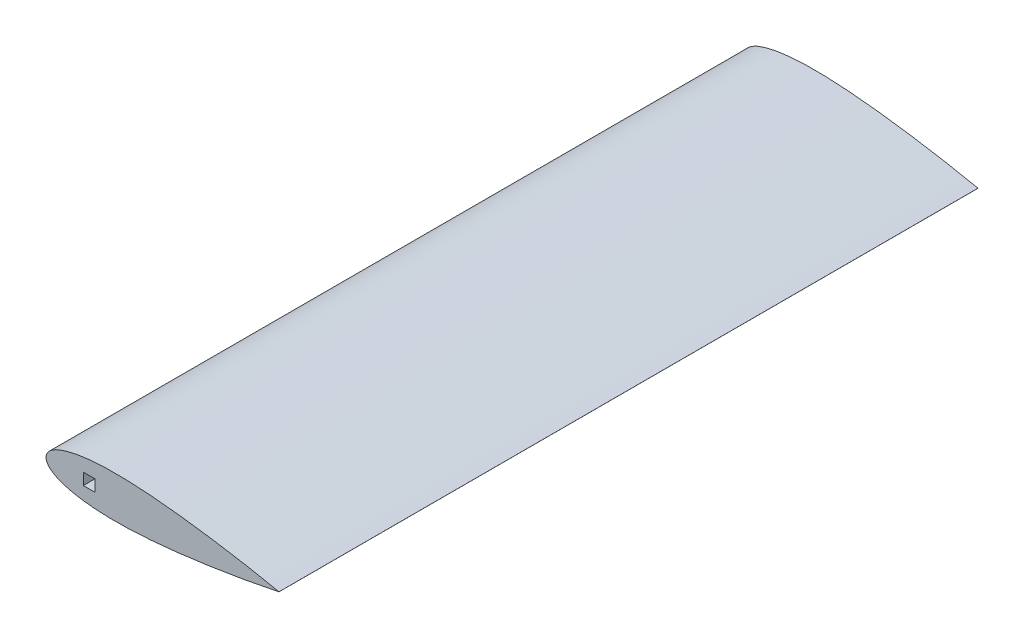
SolidWorks part; units mm, degrees
material "polystirene foam"
ref_plane "Front Plane" through (0, 0, 0) normal (0, 0, 1) x (1, 0, 0)
ref_plane "Top Plane" through (0, 0, 0) normal (0, 1, 0) x (1, 0, 0)
ref_plane "Right Plane" through (0, 0, 0) normal (1, 0, 0) x (0, 0, -1)
curve "Curve1"
  spline degree 3 poles (267.933, 0.5337, 0) (270.49, -0.1564, 0) (268.2375, 0.6665, 0) (266.5672, 1.4668, 0) (262.6756, 3.0154, 0) (257.9132, 4.5724, 0) (251.732, 6.3325, 0) (244.4112, 8.2376, 0) (235.9576, 10.2728, 0) (226.5142, 12.3893, 0) (216.1934, 14.5409, 0) (205.1313, 16.6775, 0) (193.4567, 18.7298, 0) (181.2977, 20.6324, 0) (168.7678, 22.3117, 0) (155.9753, 23.7079, 0) (143.0353, 24.8049, 0) (130.0617, 25.5802, 0) (117.1734, 26.0003, 0) (104.4837, 26.0576, 0) (92.1044, 25.7531, 0) (80.1395, 25.0742, 0) (68.69, 24.0381, 0) (57.8509, 22.6699, 0) (47.7143, 21.0125, 0) (38.3732, 19.0872, 0) (29.9084, 16.9558, 0) (22.399, 14.6444, 0) (15.9079, 12.2159, 0) (10.4843, 9.7202, 0) (6.177, 7.2209, 0) (2.9612, 4.7412, 0) (0.9766, 2.4261, 0) (0.0237, 0.7907, 0) (-0.0162, -0.4697, 0) (0.8003, -1.8361, 0) (3.4921, -2.6295, 0) (7.308, -3.6627, 0) (12.6566, -4.3991, 0) (19.3194, -5.0329, 0) (27.2905, -5.4698, 0) (36.4622, -5.7387, 0) (46.7414, -5.84, 0) (58.0105, -5.7702, 0) (70.1434, -5.5368, 0) (83.0071, -5.1408, 0) (96.4629, -4.5659, 0) (110.374, -3.827, 0) (124.6167, -2.893, 0) (139.0995, -1.7363, 0) (153.7348, -0.4008, 0) (168.4097, 0.8923, 0) (182.9339, 2.0414, 0) (197.0782, 2.9592, 0) (210.6044, 3.579, 0) (223.2667, 3.8744, 0) (234.8405, 3.8186, 0) (245.0477, 3.4533, 0) (253.7786, 2.7629, 0) (260.4407, 1.9422, 0) (265.7815, 0.9299, 0) (267.933, 0.5337, 0) (270.49, -0.1564, 0) (268.2375, 0.6665, 0) knots -0.016249 -0.007187 -0.001789 0 0.001694 0.006395 0.013462 0.022754 0.034367 0.048191 0.064031 0.081681 0.100894 0.121432 0.143025 0.165434 0.188439 0.211855 0.235496 0.259144 0.282615 0.305702 0.328232 0.35003 0.370944 0.390817 0.409506 0.426857 0.442733 0.457018 0.469615 0.48045 0.489472 0.49673 0.502329 0.506256 0.506442 0.509182 0.513914 0.521178 0.530944 0.543145 0.55767 0.574384 0.59311 0.613638 0.635744 0.659184 0.683714 0.709076 0.735036 0.76143 0.788184 0.815057 0.841645 0.867514 0.892232 0.915364 0.936485 0.9552 0.971104 0.983751 0.992813 0.998211 1 1.001694 1.006395 1.013462 periodic
curve "Curve2"
  spline degree 3 poles (1, 0.0019, 0) (0.9833, 0.0053, 0) (0.9501, 0.0122, 0) (0.8834, 0.025, 0) (0.8002, 0.0397, 0) (0.7001, 0.0553, 0) (0.6002, 0.0688, 0) (0.5002, 0.0799, 0) (0.4001, 0.0878, 0) (0.3167, 0.0906, 0) (0.25, 0.0895, 0) (0.1999, 0.0865, 0) (0.1497, 0.0808, 0) (0.1079, 0.0728, 0) (0.0746, 0.0633, 0) (0.0492, 0.0537, 0) (0.0279, 0.0421, 0) (0.0083, 0.0261, 0) (-0.0054, 0, 0) (0.0083, -0.0261, 0) (0.0279, -0.0421, 0) (0.0492, -0.0537, 0) (0.0746, -0.0633, 0) (0.1079, -0.0728, 0) (0.1497, -0.0808, 0) (0.1999, -0.0865, 0) (0.25, -0.0895, 0) (0.3167, -0.0906, 0) (0.4001, -0.0878, 0) (0.5002, -0.0799, 0) (0.6002, -0.0688, 0) (0.7001, -0.0553, 0) (0.8002, -0.0397, 0) (0.8834, -0.025, 0) (0.9501, -0.0122, 0) (0.9833, -0.0053, 0) (1, -0.0019, 0) knots 0 0 0 0 0.024604 0.049152 0.098109 0.146905 0.195555 0.244056 0.29241 0.340644 0.364754 0.388906 0.413178 0.437756 0.450305 0.46323 0.477068 0.485036 0.5 0.514964 0.522932 0.53677 0.549695 0.562244 0.586822 0.611094 0.635246 0.659356 0.70759 0.755944 0.804445 0.853095 0.901891 0.950848 0.975396 1 1 1 1
sketch "Sketch2" plane through (0, 0, 0) normal (0, 0, 1) x (1, 0, 0)
  line L1 (0, 0) -> (200, 0) construction
  line L2 (0, 5.3617) -> (0, 0) construction
  line L3 (200, 0.026) -> (200, -0.026)
  line L4 (0, 17.8541) -> (200, 17.8541) construction
  line L5 (0, -17.8541) -> (200, -17.8541) construction
  spline S1 degree 3 poles (200, 0.026) (196.1337, 0.8245) (188.9731, 2.314) (175.1972, 4.9535) (158.6821, 7.8644) (138.8483, 10.963) (119.0176, 13.6524) (99.1866, 15.8519) (79.3508, 17.4108) (62.8016, 17.9646) (49.5701, 17.7436) (39.6384, 17.1555) (29.688, 16.02) (21.4064, 14.4333) (14.8011, 12.5462) (9.7569, 10.6396) (5.5318, 8.3438) (1.6454, 5.1683) (-1.0737, 0) (1.6454, -5.1683) (5.5318, -8.3438) (9.7569, -10.6396) (14.8011, -12.5462) (21.4064, -14.4333) (29.688, -16.02) (39.6384, -17.1555) (49.5701, -17.7436) (62.8016, -17.9646) (79.3508, -17.4108) (99.1866, -15.8519) (119.0176, -13.6524) (138.8483, -10.963) (158.6821, -7.8644) (175.1972, -4.9535) (188.9731, -2.314) (196.1337, -0.8245) (200, -0.026) knots -0.00419 -0.00419 -0.00419 -0.00419 0.024604 0.049152 0.098109 0.146905 0.195555 0.244056 0.29241 0.340644 0.364754 0.388906 0.413178 0.437756 0.450305 0.46323 0.477068 0.485036 0.5 0.514964 0.522932 0.53677 0.549695 0.562244 0.586822 0.611094 0.635246 0.659356 0.70759 0.755944 0.804445 0.853095 0.901891 0.950848 0.975396 1.00419 1.00419 1.00419 1.00419
  dimension "D1" = 200
extrude "Boss-Extrude1" add sketch "Sketch2" along normal blind 600 contours S1 L3
sketch "Sketch3" plane through (0, 0, 600) normal (0, 0, 1) x (1, 0, 0)
  line L0 (0, 0) -> (20, 0)
  line L1 (0, 0) -> (200, 0) construction
  line L2 (20, 0) -> (30, 0)
  line L3 (30, 0) -> (30, -24.2417)
  line L4 (20, 0) -> (20, -24.2417)
  line L5 (20, -24.2417) -> (30, -24.2417)
  line L6 (30, 0) -> (20, 0)
  line L7 (20, 0) -> (20, -24.2417)
  line L8 (20, -24.2417) -> (30, -24.2417)
  line L9 (30, -24.2417) -> (30, 0)
sketch "Sketch5" plane through (0, 0, 0) normal (0, 0, -1) x (-1, 0, 0)
  line L0 (0, 0) -> (-18, 0)
  line L1 (0, 0) -> (-200, 0) construction
  line L2 (-18, 0) -> (-18, 13.4428)
  spline S0 degree 3 poles (-200, 0.026) (-196.1337, 0.8245) (-188.9731, 2.314) (-175.1972, 4.9535) (-158.6821, 7.8644) (-138.8483, 10.963) (-119.0176, 13.6524) (-99.1866, 15.8519) (-79.3508, 17.4108) (-62.8016, 17.9646) (-49.5701, 17.7436) (-39.6384, 17.1555) (-29.688, 16.02) (-21.4064, 14.4333) (-14.8011, 12.5462) (-9.7569, 10.6396) (-5.5318, 8.3438) (-1.6454, 5.1683) (1.0737, 0) (-1.6454, -5.1683) (-5.5318, -8.3438) (-9.7569, -10.6396) (-14.8011, -12.5462) (-21.4064, -14.4333) (-29.688, -16.02) (-39.6384, -17.1555) (-49.5701, -17.7436) (-62.8016, -17.9646) (-79.3508, -17.4108) (-99.1866, -15.8519) (-119.0176, -13.6524) (-138.8483, -10.963) (-158.6821, -7.8644) (-175.1972, -4.9535) (-188.9731, -2.314) (-196.1337, -0.8245) (-200, -0.026) knots -0.00419 -0.00419 -0.00419 -0.00419 0.024604 0.049152 0.098109 0.146905 0.195555 0.244056 0.29241 0.340644 0.364754 0.388906 0.413178 0.437756 0.450305 0.46323 0.477068 0.485036 0.5 0.514964 0.522932 0.53677 0.549695 0.562244 0.586822 0.611094 0.635246 0.659356 0.70759 0.755944 0.804445 0.853095 0.901891 0.950848 0.975396 1.00419 1.00419 1.00419 1.00419 construction
sketch "Sketch6" plane through (0, 0, 600) normal (0, 0, 1) x (1, 0, 0)
  line L0 (30, 0) -> (20, 0)
  line L1 (20, 0) -> (18, 0)
  line L2 (30, 0) -> (32, 0)
  line L3 (0, 0) -> (200, 0) construction
  line L4 (18, 0) -> (18, -22.0484)
  line L5 (18, -22.0484) -> (18, -25.4056)
  line L6 (32, 0) -> (32, -25.4056)
  line L7 (18, -25.4056) -> (32, -25.4056)
  line L8 (30, 0) -> (30, -24.2417) construction
  line L9 (20, 5) -> (30, 5)
  line L10 (20, 5) -> (20, -5)
  line L11 (20, -5) -> (30, -5)
  line L12 (30, 5) -> (30, -5)
  line L13 (20, 5) -> (30, -5) construction
  line L14 (20, -5) -> (30, 5) construction
  point P12 (25, 0)
  dimension "D1" = 10
extrude "Cut-Extrude2" cut sketch "Sketch6" against normal blind 656 contours L12 L9 L10 L0 | L12 L0 L10 L11 region at (25, -2.5, 600) region at (25, 2.5, 600)
sketch "Sketch8" plane through (0, 5, 0) normal (0, -1, 0) x (-1, 0, 0)
  line L0 (-30, -600) -> (-30, 0)
  line L1 (-30, -300) -> (-30, -350)
  line L2 (-30, -300) -> (-30, -250)
  line L13 (-30, -350) -> (-32, -350)
  line L14 (-32, -350) -> (-32, -364)
  line L15 (-32, -364) -> (-18, -364)
  line L16 (-18, -364) -> (-18, -350)
  line L17 (-30, -350) -> (-18, -350)
  line L18 (-30, -250) -> (-18, -250)
  line L19 (-18, -250) -> (-18, -236)
  line L20 (-18, -236) -> (-32, -236)
  line L21 (-32, -236) -> (-32, -250)
  line L22 (-30, -250) -> (-32, -250)
  line M3 (-30, 0) -> (-30, -600)
  line M5 (-20, -600) -> (-20, 0)
extrude "Cut-Extrude4" cut sketch "Sketch8" against normal blind 2 and the other way blind 42 contours L20 L0 L18 M5 | L17 L15 M3 M5 | L17 L15 L16 M5 | L14 L15 L13 M3 | L19 L20 L18 M5 | L22 L0 L20 L21 region at (25, 5, 357) region at (31, 5, 357) region at (19, 5, 357) region at (31, 5, 243) region at (25, 5, 243) region at (19, 5, 243)
sketch "Sketch9" plane through (32, 0, 0) normal (-1, 0, 0) x (0, 0, 1)
  line L1 (350, 7) -> (364, 7)
  line L2 (350, 7) -> (350, -7)
  line L3 (350, -7) -> (364, -7)
  line L4 (364, 7) -> (364, -7)
  dimension "D1" = 14
  dimension "D2" = 14
extrude "Cut-Extrude5" cut sketch "Sketch9" against normal blind 14
sketch "Sketch10" plane through (32, 0, 0) normal (-1, 0, 0) x (0, 0, 1)
  line L1 (236, 7) -> (250, 7)
  line L2 (236, 7) -> (236, -7)
  line L3 (236, -7) -> (250, -7)
  line L4 (250, 7) -> (250, -7)
  dimension "D1" = 14
  dimension "D2" = 14
extrude "Cut-Extrude6" cut sketch "Sketch10" against normal blind 14
sketch "Sketch11" plane through (0, 0, 600) normal (0, 0, 1) x (1, 0, 0)
  line L0 (30, 5) -> (32, 5)
  line L1 (32, 5) -> (42, 5)
  line L2 (32, 5) -> (32, -5)
  line L3 (32, -5) -> (42, -5)
  line L4 (42, -5) -> (42, 5)
extrude "Cut-Extrude7" cut sketch "Sketch11" against normal blind 654 contours L3 L4 L1 L2 region at (37, 0, 600)
sketch "Sketch12" plane through (0, 0, 600) normal (0, 0, 1) x (1, 0, 0)
  line L0 (30, 0) -> (30, -24.2417) construction
  line L1 (20, 5) -> (30, 5)
  line L2 (20, 5) -> (20, -5)
  line L3 (20, -5) -> (30, -5)
  line L4 (30, 5) -> (30, -5)
  line L5 (20, -5) -> (30, -5) construction
extrude "Boss-Extrude3" add sketch "Sketch12" against normal blind 600 contours L2 L1 L4 L3
sketch "Sketch13" plane through (0, -5, 0) normal (0, -1, 0) x (-1, 0, 0)
  line L0 (-32, -236) -> (-18, -236) construction
  line L1 (-20, -250) -> (-30, -250)
  line L2 (-20, -250) -> (-20, -236)
  line L3 (-20, -236) -> (-30, -236)
  line L4 (-30, -250) -> (-30, -236)
  line L5 (-18, -236) -> (-46, -236) construction
extrude "Cut-Extrude8" cut sketch "Sketch13" against normal blind 10
sketch "Sketch14" plane through (0, -5, 0) normal (0, -1, 0) x (-1, 0, 0)
  line L1 (-20, -364) -> (-30, -364)
  line L2 (-20, -364) -> (-20, -350)
  line L3 (-20, -350) -> (-30, -350)
  line L4 (-30, -364) -> (-30, -350)
extrude "Cut-Extrude9" cut sketch "Sketch14" against normal blind 10
sketch "Sketch15" plane through (46, 0, 0) normal (-1, 0, 0) x (0, 0, 1)
  line L0 (350, 7) -> (350, -7)
  line L1 (350, 7) -> (350, -7) construction
  line L2 (350, -7) -> (364, -7)
  line L3 (350, 7) -> (364, 7)
  line L4 (364, 7) -> (350, 7) construction
  line L5 (364, 7) -> (364, -7)
sketch "Sketch16" plane through (46, 0, 0) normal (-1, 0, 0) x (0, 0, 1)
  line L0 (350, -7) -> (350, -2.5)
  line L1 (350, -7) -> (364, -7)
  line L2 (364, -7) -> (364, -2.5)
  line L3 (364, -2.5) -> (350, -2.5)
  line L5 (350, -2.5) -> (364, -2.5)
  line L6 (350, -2.5) -> (350, -7)
  line L7 (350, -7) -> (364, -7)
  line L8 (364, -2.5) -> (364, -7)
  line M1 (350, 7) -> (350, -7)
  line M2 (350, -7) -> (364, -7)
  line M3 (364, -7) -> (364, 7)
extrude "Cut-Extrude10" cut sketch "Sketch16" against normal blind 10 contours L3 M3 M1 M2 region at (46, -4.75, 357)
sketch "Sketch17" plane through (46, 0, 0) normal (-1, 0, 0) x (0, 0, 1)
  line L0 (350, 7) -> (350, -7)
  line L1 (350, -7) -> (364, -7)
  line L2 (364, -7) -> (364, 2)
  line L3 (364, 2) -> (350, 2)
  line L4 (350, 2) -> (350, -7)
  line M1 (350, -2.5) -> (364, -2.5)
  line M2 (364, -2.5) -> (364, 7)
extrude "Cut-Extrude11" cut sketch "Sketch17" against normal blind 14 contours L3 L0 M2 M1 region at (46, -0.25, 357)
